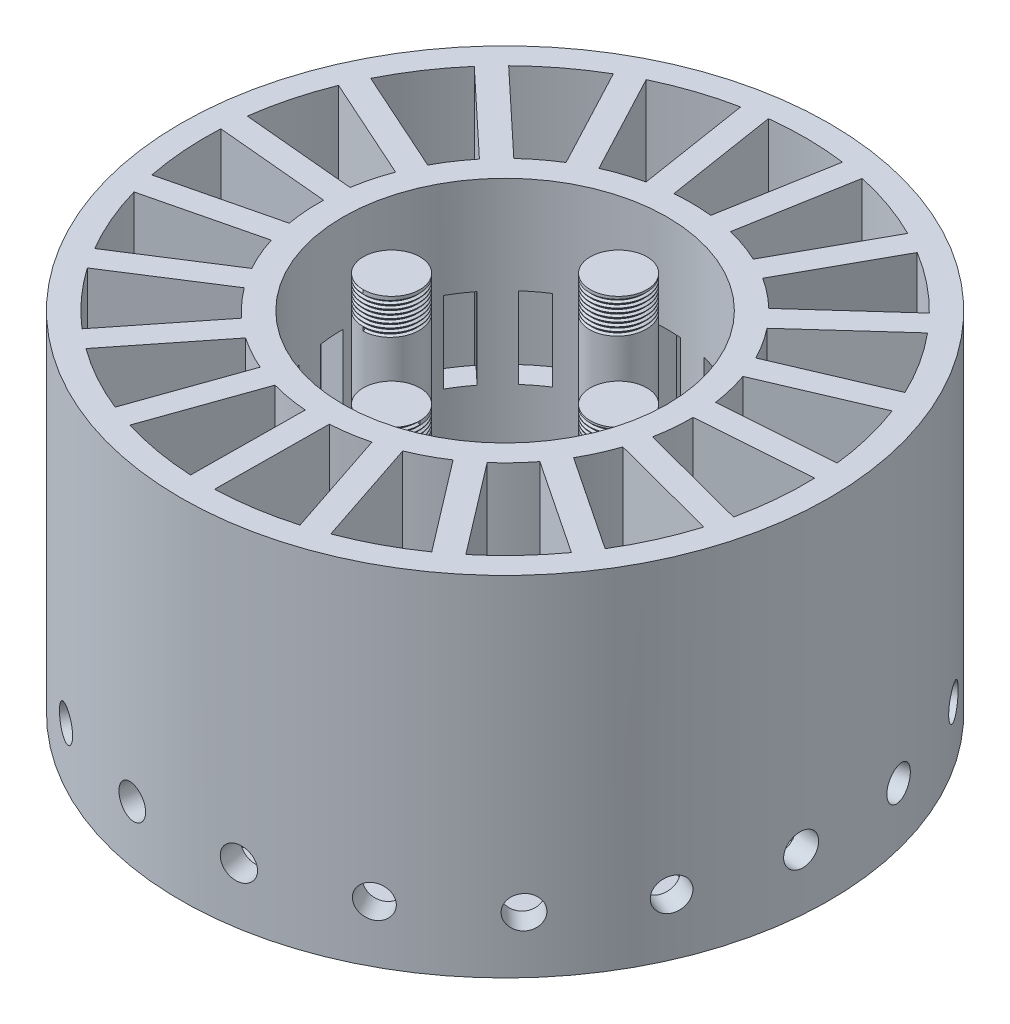
SolidWorks part; units mm, degrees
ref_plane "Front Plane" through (0, 0, 0) normal (0, 0, 1) x (1, 0, 0)
ref_plane "Top Plane" through (0, 0, 0) normal (0, 1, 0) x (1, 0, 0)
ref_plane "Right Plane" through (0, 0, 0) normal (1, 0, 0) x (0, 0, -1)
sketch "Sketch1" plane through (0, 0, 0) normal (0, 1, 0) x (1, 0, 0)
  circle A0 centre (0, 0) radius 20
  circle A1 centre (0, 0) radius 18.5
  dimension "D1" = 40
  dimension "D2" = 1.5
extrude "Boss-Extrude1" add sketch "Sketch1" along normal blind 20
sketch "Sketch2" plane through (0, 0, 0) normal (0, 0, 1) x (1, 0, 0)
  line L0 (0, 0) -> (0, 20) construction
  line L1 (20, 20) -> (-20, 20) construction
  circle A0 centre (0, 2) radius 1
  dimension "D1" = 2
  dimension "D2" = 2
extrude "Cut-Extrude1" cut sketch "Sketch2" against normal up to surface (19.975 mm away) up to face at (0, 20, 20)
pattern_circular "CirPattern1" count 19 over 360 about axis through (0, 0, 0) along (0, 1, 0) of "Cut-Extrude1"
sketch "Sketch3" plane through (0, 0, 0) normal (0, 1, 0) x (1, 0, 0)
  line L0 (-1, 0) -> (1, 0) construction
  line L1 (-18.7854, 0) -> (-17.6525, -6.425)
  line L2 (9.3927, 16.2686) -> (3.262, 18.5)
  line L3 (3.262, 18.5) -> (-3.262, 18.5)
  line L4 (-3.262, 18.5) -> (-9.3927, 16.2686)
  line L5 (-9.3927, 16.2686) -> (-14.3904, 12.075)
  line L6 (-14.3904, 12.075) -> (-17.6525, 6.425)
  line L7 (-17.6525, 6.425) -> (-18.7854, 0)
  line L8 (-17.6525, -6.425) -> (-14.3904, -12.075)
  line L9 (-14.3904, -12.075) -> (-9.3927, -16.2686)
  line L10 (-9.3927, -16.2686) -> (-3.262, -18.5)
  line L11 (-3.262, -18.5) -> (3.262, -18.5)
  line L12 (3.262, -18.5) -> (9.3927, -16.2686)
  line L13 (9.3927, -16.2686) -> (14.3904, -12.075)
  line L14 (14.3904, -12.075) -> (17.6525, -6.425)
  line L15 (17.6525, -6.425) -> (18.7854, 0)
  line L16 (18.7854, 0) -> (17.6525, 6.425)
  line L17 (17.6525, 6.425) -> (14.3904, 12.075)
  line L18 (14.3904, 12.075) -> (9.3927, 16.2686)
  line L19 (0.9979, 9.9783) -> (2.5234, 18.6302)
  line L20 (0.9979, 9.9783) -> (2.4751, 9.7178)
  line L21 (2.5234, 18.6302) -> (4.0007, 18.3698)
  line L22 (2.4751, 9.7178) -> (4.0007, 18.3698)
  line L23 (0.9979, 9.9783) -> (4.0007, 18.3698) construction
  line L24 (2.5234, 18.6302) -> (2.4751, 9.7178) construction
  line L25 (3.262, 18.5) -> (0, 0) construction
  line L26 (8.4359, 16.8014) -> (9.7485, 16.0754)
  line L27 (4.1838, 9.1137) -> (8.4359, 16.8014)
  line L28 (4.1838, 9.1137) -> (5.4964, 8.3876)
  line L29 (5.4964, 8.3876) -> (9.7485, 16.0754)
  line L30 (13.4343, 13.1519) -> (14.44, 12.0391)
  line L31 (6.9163, 7.2614) -> (13.4343, 13.1519)
  line L32 (6.9163, 7.2614) -> (7.922, 6.1485)
  line L33 (7.922, 6.1485) -> (14.44, 12.0391)
  line L34 (16.9768, 8.0772) -> (17.5667, 6.6981)
  line L35 (8.8993, 4.6222) -> (16.9768, 8.0772)
  line L36 (8.8993, 4.6222) -> (9.4892, 3.2431)
  line L37 (9.4892, 3.2431) -> (17.5667, 6.6981)
  line L38 (18.6796, 2.1272) -> (18.7898, 0.6313)
  line L39 (9.9179, 1.4822) -> (18.6796, 2.1272)
  line L40 (9.9179, 1.4822) -> (10.0281, -0.0138)
  line L41 (10.0281, -0.0138) -> (18.7898, 0.6313)
  line L42 (18.3582, -4.0533) -> (17.9767, -5.504)
  line L43 (9.8618, -1.8185) -> (18.3582, -4.0533)
  line L44 (9.8618, -1.8185) -> (9.4803, -3.2691)
  line L45 (9.4803, -3.2691) -> (17.9767, -5.504)
  line L46 (16.0474, -9.7946) -> (15.2155, -11.0427)
  line L47 (8.737, -4.9221) -> (16.0474, -9.7946)
  line L48 (8.737, -4.9221) -> (7.9051, -6.1702)
  line L49 (7.9051, -6.1702) -> (15.2155, -11.0427)
  line L50 (11.9976, -14.4745) -> (10.8055, -15.3849)
  line L51 (6.6654, -7.4923) -> (11.9976, -14.4745)
  line L52 (6.6654, -7.4923) -> (5.4733, -8.4027)
  line L53 (5.4733, -8.4027) -> (10.8055, -15.3849)
  line L54 (6.6477, -17.5858) -> (5.2246, -18.0598)
  line L55 (3.8715, -9.2506) -> (6.6477, -17.5858)
  line L56 (3.8715, -9.2506) -> (2.4484, -9.7246)
  line L57 (2.4484, -9.7246) -> (5.2246, -18.0598)
  line L58 (0.5774, -18.7915) -> (-0.9225, -18.7777)
  line L59 (0.6581, -10.0065) -> (0.5774, -18.7915)
  line L60 (0.6581, -10.0065) -> (-0.8418, -9.9927)
  line L61 (-0.8418, -9.9927) -> (-0.9225, -18.7777)
  line L62 (-5.5555, -17.9608) -> (-6.9697, -17.4607)
  line L63 (-2.6266, -9.678) -> (-5.5555, -17.9608)
  line L64 (-2.6266, -9.678) -> (-4.0408, -9.1779)
  line L65 (-4.0408, -9.1779) -> (-6.9697, -17.4607)
  line L66 (-11.0863, -15.1838) -> (-12.2615, -14.2516)
  line L67 (-5.6268, -8.3007) -> (-11.0863, -15.1838)
  line L68 (-5.6268, -8.3007) -> (-6.802, -7.3686)
  line L69 (-6.802, -7.3686) -> (-12.2615, -14.2516)
  line L70 (-15.4158, -10.7614) -> (-16.2246, -9.4981)
  line L71 (-8.0171, -6.024) -> (-15.4158, -10.7614)
  line L72 (-8.0171, -6.024) -> (-8.826, -4.7607)
  line L73 (-8.826, -4.7607) -> (-16.2246, -9.4981)
  line L74 (-18.0747, -5.1728) -> (-18.4296, -3.7154)
  line L75 (-9.5387, -3.0944) -> (-18.0747, -5.1728)
  line L76 (-9.5387, -3.0944) -> (-9.8936, -1.637)
  line L77 (-9.8936, -1.637) -> (-18.4296, -3.7154)
  line L78 (-18.775, 0.9764) -> (-18.6374, 2.47)
  line L79 (-10.0266, 0.1705) -> (-18.775, 0.9764)
  line L80 (-10.0266, 0.1705) -> (-9.889, 1.6641)
  line L81 (-9.889, 1.6641) -> (-18.6374, 2.47)
  line L82 (-17.4407, 7.0197) -> (-16.8256, 8.3877)
  line L83 (-9.428, 3.4169) -> (-17.4407, 7.0197)
  line L84 (-9.428, 3.4169) -> (-8.8129, 4.7849)
  line L85 (-8.8129, 4.7849) -> (-16.8256, 8.3877)
  line L86 (-14.2164, 12.3023) -> (-13.1904, 13.3965)
  line L87 (-7.8077, 6.293) -> (-14.2164, 12.3023)
  line L88 (-7.8077, 6.293) -> (-6.7817, 7.3872)
  line L89 (-6.7817, 7.3872) -> (-13.1904, 13.3965)
  line L90 (-9.4516, 16.2518) -> (-8.1259, 16.9536)
  line L91 (-5.3413, 8.4872) -> (-9.4516, 16.2518)
  line L92 (-5.3413, 8.4872) -> (-4.0156, 9.189)
  line L93 (-4.0156, 9.189) -> (-8.1259, 16.9536)
  line L94 (-3.6625, 18.4402) -> (-2.1808, 18.6734)
  line L95 (-2.2961, 9.7617) -> (-3.6625, 18.4402)
  line L96 (-2.2961, 9.7617) -> (-0.8144, 9.995)
  line L97 (-0.8144, 9.995) -> (-2.1808, 18.6734)
  circle A0 centre (0, 0) radius 10
  circle A1 centre (0, 0) radius 11.5
  circle A3 centre (0, 0) radius 18.5 construction
  circle A4 centre (0, 0) radius 18.5 construction
  point P5 (0, 18.5)
  point P28 (2.4993, 14.174)
  dimension "D2" = 1.5
  dimension "D1" = 20
  dimension "D3" = 1.5
  dimension "D4" = 19
extrude "Boss-Extrude6" add sketch "Sketch3" along normal up to surface (20 mm away) contours A1 L93 L3 L4 L91 | L27 A1 L22 L20 A0 L28 | L22 A1 L19 L20 | L29 A1 L27 L28 | L31 A1 L29 L28 A0 L32 | L33 A1 L31 L32 | A1 L22 L2 L3 L19 | A1 L29 L18 L2 L27 | A1 L33 L17 L18 L31 | L93 A1 L91 L92 | L19 A1 L93 L92 A0 L20 | L35 A1 L33 L32 A0 L36 | L37 A1 L35 L36 | A1 L37 L16 L17 L35 | L39 A1 L37 L36 A0 L40 | L41 A1 L39 L40 | A1 L41 L15 L16 L39 | L43 A1 L41 L40 A0 L44 | A1 L45 L14 L15 L43 | L47 A1 L45 L44 A0 L48 | L49 A1 L47 L48 | A1 L49 L13 L14 L47 | L51 A1 L49 L48 A0 L52 | L53 A1 L51 L52 | A1 L53 L12 L13 L51 | L55 A1 L53 L52 A0 L56 | L57 A1 L55 L56 | A1 L57 L11 L12 L55 | L59 A1 L57 L56 A0 L60 | L61 A1 L59 L60 | A1 L61 L10 L11 L59 | L63 A1 L61 L60 A0 L64 | L65 A1 L63 L64 | A1 L65 L9 L10 L63 | L67 A1 L65 L64 A0 L68 | L69 A1 L67 L68 | A1 L69 L8 L9 L67 | L71 A1 L69 L68 A0 L72 | L73 A1 L71 L72 | A1 L73 L1 L8 L71 | L75 A1 L73 L72 A0 L76 | L77 A1 L75 L76 | A1 L77 L7 L1 L75 | L79 A1 L77 L76 A0 L80 | L81 A1 L79 L80 | A1 L81 L6 L7 L79 | L83 A1 L81 L80 A0 L84 | L85 A1 L83 L84 | A1 L85 L5 L6 L83 | L87 A1 L85 L84 A0 L88 | L89 A1 L87 L88 | L91 A1 L89 L88 A0 L92 | A1 L89 L4 L5 L87 | L45 A1 L43 L44 | L95 A1 L93 L92 A0 L96 | L97 A1 L95 L96 | A1 L97 L3 L4 L95 | L44 L45 L42 L43 region at (-14.5885, 0, 3.5538) region at (-14.9646, 0, -1.3763) region at (-10.731, 0, 0.79) region at (-10.4409, 0, 2.5422) region at (-10.7006, 0, -0.9857) region at (-9.893, 0, 4.2316) region at (-10.4061, 0, -2.7371) region at (-12.6365, 0, 8.0926) region at (-9.0497, 0, 5.7946) region at (-13.7214, 0, -6.1667) region at (-9.8008, 0, -4.4068) region at (-7.983, 0, 7.2145) region at (-8.9535, 0, -5.9677) region at (-9.3206, 0, 11.752) region at (-6.6779, 0, 8.4191) region at (-5.2079, 0, 9.4157) region at (-7.8389, 0, -7.3503) region at (-10.9898, 0, -10.3006) region at (-6.5307, 0, -8.5515) region at (-1.8685, 0, 10.5966) region at (-3.5824, 0, 10.1312) region at (-5.0275, 0, -9.4974) region at (-3.4001, 0, -10.2087) region at (-4.9991, 0, 14.1385) region at (1.6735, 0, 10.6291) region at (-0.0987, 0, 10.7455) region at (-7.0604, 0, -13.3301) region at (-1.6713, 0, -10.6152) region at (0.0988, 0, -10.7596) region at (5.0341, 0, 9.5098) region at (3.3957, 0, 10.1953) region at (1.866, 0, -10.5827) region at (3.5871, 0, -10.1445) region at (-0.138, 0, 14.9957) region at (7.8491, 0, 7.36) region at (6.5221, 0, 8.5403) region at (-2.3509, 0, -14.9163) region at (5.2011, 0, -9.4034) region at (6.6867, 0, -8.4301) region at (4.7391, 0, 14.2311) region at (9.8136, 0, 4.4126) region at (8.9418, 0, 5.9599) region at (2.6231, 0, -14.8762) region at (7.9726, 0, -7.2051) region at (9.0616, 0, -5.8022) region at (9.1066, 0, 11.9265) region at (10.7147, 0, 0.987) region at (10.3924, 0, 2.7336) region at (7.3108, 0, -13.2126) region at (9.8801, 0, -4.226) region at (10.4546, 0, -2.5455) region at (12.4932, 0, 8.329) region at (11.1938, 0, -10.1114) region at (10.7169, 0, -0.789) region at (14.5328, 0, 3.8249) region at (13.85, 0, -5.9207) region at (15.0031, 0, -1.1018) up to face at (0, 20, 20)
sketch "Sketch5" plane through (0, 0, 0) normal (0, -1, 0) x (1, 0, 0)
  circle A0 centre (0, 0) radius 20
  circle A1 centre (0, 0) radius 20 construction
extrude "Boss-Extrude11" add sketch "Sketch5" along normal blind 1.5
ref_plane "Plane1" through (0, 9, 0) normal (0, 1, 0) x (1, 0, 0)
sketch "Sketch6" plane through (0, 9, 0) normal (0, 1, 0) x (1, 0, 0)
  line L2 (2.6163, 9.6517) -> (2.8777, 11.1341)
  line L3 (4.0323, 9.151) -> (4.7609, 10.4682)
  line L4 (4.2004, 11.8789) -> (0, 0) construction
  line L6 (2.7313, 11.1709) -> (3.9485, 18.0737) construction
  arc A2 (4.8979, 10.4048) -> (2.7313, 11.1709) centre (0, 0) ccw construction
  circle A3 centre (0, 0) radius 10 construction
  arc A4 (2.8777, 11.1341) -> (4.7609, 10.4682) centre (0, 0) cw
  arc A8 (2.6163, 9.6517) -> (4.0323, 9.151) centre (0, 0) cw
  circle A9 centre (0, 0) radius 10 construction
  point P2 (3.3337, 9.4279)
  point P4 (3.8338, 10.8421)
  dimension "D1" = 2
extrude "Cut-Extrude2" cut sketch "Sketch6" along normal blind 5
pattern_circular "CirPattern2" count 19 over 360 about axis through (0, 0, 0) along (0, 1, 0) of "Cut-Extrude2" reverse direction yes
sketch "Sketch7" plane through (0, 0, 0) normal (0, 1, 0) x (1, 0, 0)
  circle A0 centre (0, 7) radius 1.75
  circle A1 centre (7, 0) radius 1.75
  circle A2 centre (0, -7) radius 1.75
  circle A3 centre (-7, 0) radius 1.75
  dimension "D1" = 3.5
  dimension "D2" = 7
  dimension "D3" = 4
extrude "Boss-Extrude12" add sketch "Sketch7" along normal blind 18.5 contours A0 region at (0, 0, -7)
thread "Thread1" pitch 0.25 method cut profile "Thread Profile1" start angle 0, offset 0, length 2, pitch 0.25, diameter 3.5
ref_plane "Plane2" through (-1.75, 18.5, -7) normal (0, 0, 1) x (-1, 0, 0)
sketch "Thread Profile1" plane through (-1.75, 18.5, -7) normal (0, 0, 1) x (-1, 0, 0)
  line L0 (0, 0) -> (0, 0.25) construction
  line L11 (0, 0) -> (0, 0.2187)
  line L12 (0, 0.2187) -> (-0.1353, 0.1406)
  line L13 (-0.1353, 0.1406) -> (-0.1353, 0.0781)
  line L15 (-0.1353, 0.0781) -> (0, 0)
  line L17 (-0.1353, 0.1094) -> (0, 0.1094) construction
  point P2 (0, 0)
  dimension "Pitch" = 0.25
  dimension "Profile_Angle" = 60
  dimension "Profile_Land" = 0.0625
  dimension "Profile_Height" = 0.1353
pattern_circular "CirPattern3" count 4 over 360 about axis through (0, 0, 0) along (0, 1, 0) of "Boss-Extrude12", "Thread1" reverse direction yes
sketch "Sketch22" plane through (0, 0, 0) normal (0, 1, 0) x (1, 0, 0)
  circle A0 centre (0, 0) radius 2.5
  dimension "D1" = 5
extrude "Cut-Extrude5" cut sketch "Sketch22" against normal through all
equation "\"diameter_ring_outer\"= 40mm"
equation "\"height_ring\"= 20mm"
equation "\"D1@Sketch1\"=\"diameter_ring_outer\""
equation "\"D2@Sketch1\"=\"width_wall\""
equation "\"D1@Boss-Extrude1\"=\"height_ring\""
equation "\"D1@Sketch2\"=\"diameter_tube\""
equation "\"dist_tube_bottom\"= 1mm"
equation "\"D2@Sketch2\"=\"diameter_tube\"/2+\"dist_tube_bottom\""
equation "\"diameter_ring_inner\"= 20mm"
equation "\"D1@Sketch3\"=\"diameter_ring_inner\""
equation "\"D3@Sketch3\"=\"width_wall\""
equation "\"length_spring_expand\"= 15mm"
equation "\"length_spring_compress\"= 7.5mm"
equation "\"D1@Boss-Extrude11\" = \"width_wall\""
equation "\"height_slit\"= 5mm"
equation "\"D1@Cut-Extrude2\"=\"height_slit\""
equation "\"diameter_spring_inner\"= 3.5mm"
equation "\"D1@Sketch7\"=\"diameter_spring_inner\""
equation "\"D1@Boss-Extrude12\"=\"length_spring_expand\"+\"width_wall\"+\"height_thread\""
equation "\"D2@Sketch3\"=\"width_wall\""
equation "\"length_slit\"= 2mm"
equation "\"D4@Thread1\"=\"height_thread\""
equation "\"num_electrodes\"= 19"
equation "\"D1@CirPattern1\"=\"num_electrodes\""
equation "\"D4@Sketch3\"=\"num_electrodes\""
equation "\"D1@CirPattern2\"=\"num_electrodes\""
equation "\"diameter_screw_Cz\"= 5mm"
equation "\"D1@Sketch22\"=\"diameter_screw_Cz\""
equation "\"dist_spring_center\"= 7mm"
equation "\"D2@Sketch7\"=\"dist_spring_center\""
equation "\"height_thread\"= 2mm"
equation "\"width_wall\"= 1.5mm"
equation "\"diameter_tube\"= 2mm"
equation "\"depth_hold_slit\"= 1mm"
equation "\"width_hold_slit\"= 2mm"
equation "\"dist_spring_edge\"= 2mm"
